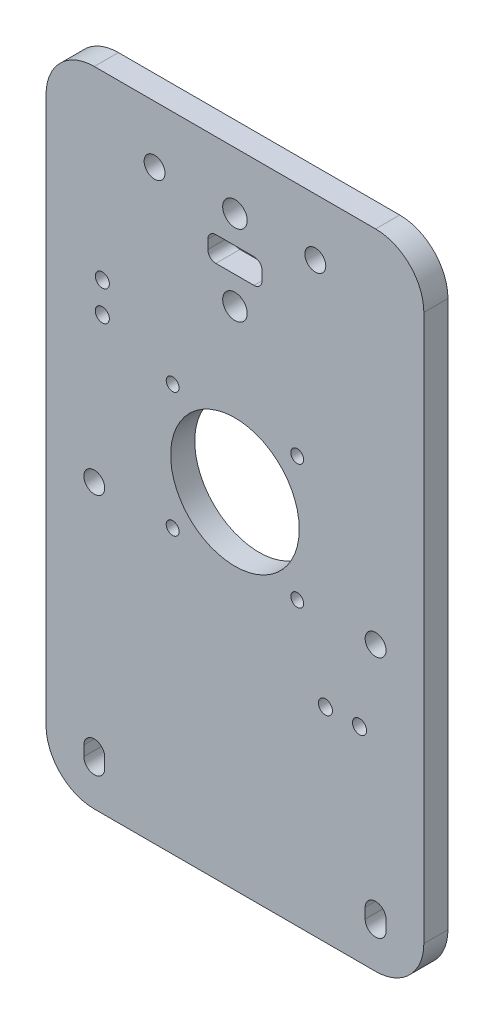
SolidWorks part; units mm, degrees
material "Acrylic (Medium-high impact)"
ref_plane "Спереди" through (0, 0, 0) normal (0, 0, 1) x (1, 0, 0)
ref_plane "Сверху" through (0, 0, 0) normal (0, 1, 0) x (1, 0, 0)
ref_plane "Справа" through (0, 0, 0) normal (1, 0, 0) x (0, 0, -1)
sketch "Model" plane through (0, 0, 0) normal (0, 0, 1) x (1, 0, 0)
  line L0 (-2.3021, 85.8) -> (5.2264, 85.8) construction
  line L1 (6.75, 135.8) -> (-6.75, 135.8) construction
  line L5 (0, 27.6115) -> (0, 21.6925) construction
  line L7 (-15.5, 9.9369) -> (-15.5, 9.0934) construction
  line L8 (15.5, 9.9369) -> (15.5, 9.0934) construction
  line L24 (-35, 37.2847) -> (-35, 77.3985) construction
  line L25 (-31.4983, 12.5) -> (-38.4, 12.5) construction
  line L26 (-31.4983, 10) -> (-38.4, 10) construction
  line L27 (-35, 12.5) -> (-35, 10) construction
  line L28 (-32.4, 12.5) -> (-32.4, 10)
  line L29 (-37.6, 12.5) -> (-37.6, 10)
  line L40 (31.4983, 10) -> (38.4, 10) construction
  line L41 (31.4983, 12.5) -> (38.4, 12.5) construction
  line L42 (35, 37.2847) -> (35, 77.3985) construction
  line L43 (35, 12.5) -> (35, 10) construction
  line L44 (32.4, 12.5) -> (32.4, 10)
  line L45 (37.6, 12.5) -> (37.6, 10)
  line L47 (-26.0102, 145.8) -> (26.0946, 145.8) construction
  line L48 (0, 129.408) -> (0, 90.7064) construction
  line L51 (-38.85, 70.45) -> (-29.8907, 70.45) construction
  line L53 (-16.3166, 125.8) -> (17.7871, 125.8) construction
  line L58 (38.85, 70.45) -> (29.8907, 70.45) construction
  line L4875 (-35, 160) -> (35, 160)
  line L4882 (47, 148) -> (47, 12)
  line L4889 (35, 0) -> (-35, 0)
  line L4896 (-47, 12) -> (-47, 148)
  line L5609 (6.75, 138.9) -> (-6.75, 138.9)
  line L5610 (-6.75, 138.9) -> (-6.75, 132.7)
  line L5611 (-6.75, 132.7) -> (6.75, 132.7)
  line L5612 (6.75, 132.7) -> (6.75, 138.9)
  line L6648 (-6.75, 138.9) -> (6.75, 138.9)
  line L6649 (6.75, 138.9) -> (6.75, 132.7)
  line L6650 (6.75, 132.7) -> (-6.75, 132.7)
  line L6651 (-6.75, 132.7) -> (-6.75, 138.9)
  arc A0 (-47, 12) -> (-35, 0) centre (-35, 12) ccw
  arc A1 (35, 0) -> (47, 12) centre (35, 12) ccw
  arc A2 (47, 148) -> (35, 160) centre (35, 148) ccw
  arc A3 (-35, 160) -> (-47, 148) centre (-35, 148) ccw
  circle A4 centre (0, 85.8) radius 16
  arc A13 (-32.4, 12.5) -> (-37.6, 12.5) centre (-35, 12.5) ccw
  arc A14 (-37.6, 10) -> (-32.4, 10) centre (-35, 10) ccw
  arc A19 (32.4, 12.5) -> (37.6, 12.5) centre (35, 12.5) cw
  arc A20 (37.6, 10) -> (32.4, 10) centre (35, 10) cw
  circle A29 centre (0, 145.8) radius 3.05
  circle A30 centre (-20, 145.8) radius 2.6
  circle A31 centre (20, 145.8) radius 2.6
  circle A32 centre (-35, 70.45) radius 2.6
  circle A33 centre (0, 125.8) radius 3.05
  circle A36 centre (35, 70.45) radius 2.6
  point P17 (0, 0)
  point P77 (-35, 11.25)
  point P114 (35, 11.25)
  point P127 (0, 160)
  dimension "D5" = 32
  dimension "D30" = 5.2
  dimension "D33" = 5.2
  dimension "D35" = 6.1
  dimension "D2" = 70
  dimension "D3" = 160
  dimension "D6" = 15.5
  dimension "D15" = 12
  dimension "D16" = 2.5
  dimension "D17" = 10
  dimension "D18" = 5.2
  dimension "D25" = 14.2
  dimension "D34" = 20
  dimension "D41" = 13.5
  dimension "D42" = 6.2
  dimension "D52" = 40
  dimension "D9" = 70
  dimension "D10" = 57.95
  dimension "D12" = 20
  dimension "D13" = 20
  dimension "D11" = 10
extrude "Base" add sketch "Model" along normal blind 6 contours L4875 A3 L4896 A0 L4889 A1 L4882 A2 L45 A20 L44 A19 region at (0, 158.1443, 0)
sketch "Sketch1" plane through (0, 0, 6) normal (0, 0, 1) x (1, 0, 0)
  line L1 (-35, 160) -> (35, 160) construction
  line L2 (-47, 12) -> (-47, 148) construction
  circle A0 centre (-33, 115) radius 1.75
  circle A1 centre (-33, 107.5) radius 1.75
  dimension "D1" = 3.5
  dimension "D3" = 7.5
  dimension "D4" = 14
  dimension "D5" = 45
extrude "SensorMount" cut sketch "Sketch1" against normal through all contours A1 | A0
sketch "Sketch2" plane through (0, 0, 6) normal (0, 0, 1) x (1, 0, 0)
  line L0 (35, 0) -> (-35, 0) construction
  line L1 (-47, 12) -> (-47, 148) construction
  circle A0 centre (22.5, 50.76) radius 1.75
  circle A1 centre (31, 50.76) radius 1.75
  dimension "D1" = 3.5
  dimension "D3" = 8.5
  dimension "D4" = 50.76
  dimension "D5" = 69.5
extrude "CableMount" cut sketch "Sketch2" against normal blind 10 contours A0 | A1
fillet "FilletCableSlot" radius 2 4 edges at (6.75, 138.9, 3) (-6.75, 138.9, 3) (-6.75, 132.7, 3) (6.75, 132.7, 3)
hole_wizard "Ø3.2 (3.2) Stepper mount Holes" positions "Sketch6" profile "Sketch7" hole size "Ø3.2" standard "ANSI Metric" end condition through all
sketch "Sketch6" plane through (0, 0, 6) normal (0, 0, 1) x (1, 0, 0)
  line L0 (-50.1491, 85.8) -> (50.1491, 85.8) construction
  line L2 (0, 0) -> (0, 95.4376) construction
  line L3 (35, 0) -> (-35, 0) construction
  circle A0 centre (0, 85.8) radius 16 construction
  point P0 (-15.5, 101.3)
  point P3 (-15.5, 70.3)
  point P6 (15.5, 70.3)
  point P9 (15.5, 101.3)
  point P22 (0, 85.8)
  point P33 (0, 0)
  dimension "D1" = 31
  dimension "D2" = 31
sketch "Sketch7" plane through (-15.5, 101.3, 6) normal (1, 0, 0) x (0, -1, 0)
  line L0 (0, 0) -> (0, 6)
  line L1 (0, 6) -> (1.6, 6)
  line L2 (1.6, 6) -> (1.6, 0)
  line L5 (1.6, 0) -> (0, 0)
  line L11 (0, -6.35) -> (0, 107.95) construction
  dimension "Thru Hole Dia." = 3.2
  dimension "Thru Hole Depth" = 6
equation "\"D11@Model\"=\"D34@Model\"/2"
